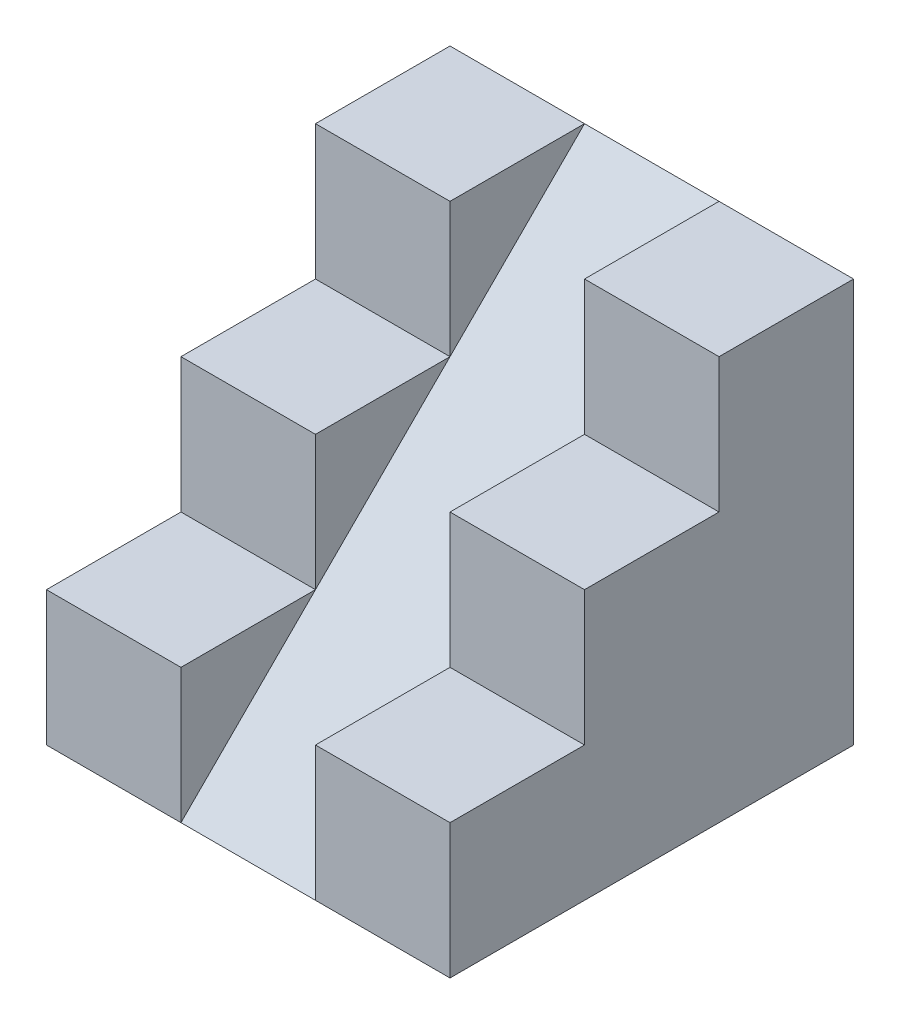
SolidWorks part; units mm, degrees
ref_plane "Alzado" through (0, 0, 0) normal (0, 0, 1) x (1, 0, 0)
ref_plane "Planta" through (0, 0, 0) normal (0, 1, 0) x (1, 0, 0)
ref_plane "Vista lateral" through (0, 0, 0) normal (1, 0, 0) x (0, 0, -1)
sketch "Croquis1" plane through (0, 0, 0) normal (0, 1, 0) x (1, 0, 0)
  line L0 (0, -30) -> (0, 30) construction
  line L1 (30, 30) -> (10, 30)
  line L2 (30, 30) -> (30, -30)
  line L3 (30, -30) -> (10, -30)
  line L4 (-30, 30) -> (-30, -30)
  line L5 (30, 30) -> (-30, -30) construction
  line L6 (30, -30) -> (-30, 30) construction
  line L7 (10, -30) -> (10, 30)
  line L8 (-10, -30) -> (-10, 30)
  line L9 (-10, 30) -> (-30, 30)
  line L10 (-10, -30) -> (-30, -30)
  point P0 (0, 0)
  dimension "D1" = 60
  dimension "D2" = 60
  dimension "D3" = 10
  dimension "D4" = 10
extrude "Saliente-Extruir1" add sketch "Croquis1" along normal blind 20
sketch "Croquis2" plane through (0, 20, 0) normal (0, 1, 0) x (1, 0, 0)
  line L0 (30, 30) -> (10, 30)
  line L1 (10, 30) -> (10, -10)
  line L2 (10, 30) -> (10, -30) construction
  line L3 (10, -10) -> (30, -10)
  line L4 (30, -30) -> (30, 30) construction
  line L5 (30, -10) -> (30, 30)
  line L6 (-10, 30) -> (-30, 30)
  line L7 (-30, 30) -> (-30, -10)
  line L8 (-30, 30) -> (-30, -30) construction
  line L9 (-30, -10) -> (-10, -10)
  line L10 (-10, -30) -> (-10, 30) construction
  line L11 (-10, -10) -> (-10, 30)
  dimension "D1" = 40
  dimension "D2" = 40
extrude "Saliente-Extruir2" add sketch "Croquis2" along normal blind 20
sketch "Croquis3" plane through (0, 40, 0) normal (0, 1, 0) x (1, 0, 0)
  line L0 (30, 30) -> (10, 30)
  line L1 (10, 30) -> (10, 10)
  line L2 (10, 30) -> (10, -10) construction
  line L3 (10, 10) -> (30, 10)
  line L4 (30, -10) -> (30, 30) construction
  line L5 (30, 10) -> (30, 30)
  line L13 (-10, 30) -> (-30, 30)
  line L14 (-30, 30) -> (-30, 10)
  line L15 (-30, 30) -> (-30, -10) construction
  line L16 (-30, 10) -> (-10, 10)
  line L17 (-10, -10) -> (-10, 30) construction
  line L18 (-10, 10) -> (-10, 30)
  dimension "D1" = 20
  dimension "D2" = 20
extrude "Saliente-Extruir3" add sketch "Croquis3" along normal blind 20
sketch "Croquis4" plane through (0, 60, 0) normal (0, 1, 0) x (1, 0, 0)
  line L0 (10, 30) -> (-10, 30)
  line L1 (-10, 30) -> (-10, -30)
  line L2 (-10, -30) -> (10, -30)
  line L3 (10, -30) -> (10, 30)
extrude "Saliente-Extruir9" add sketch "Croquis4" against normal blind 60 separate body
chamfer "Chaflán1" distance 60 1 edges at (0, 60, 30)
